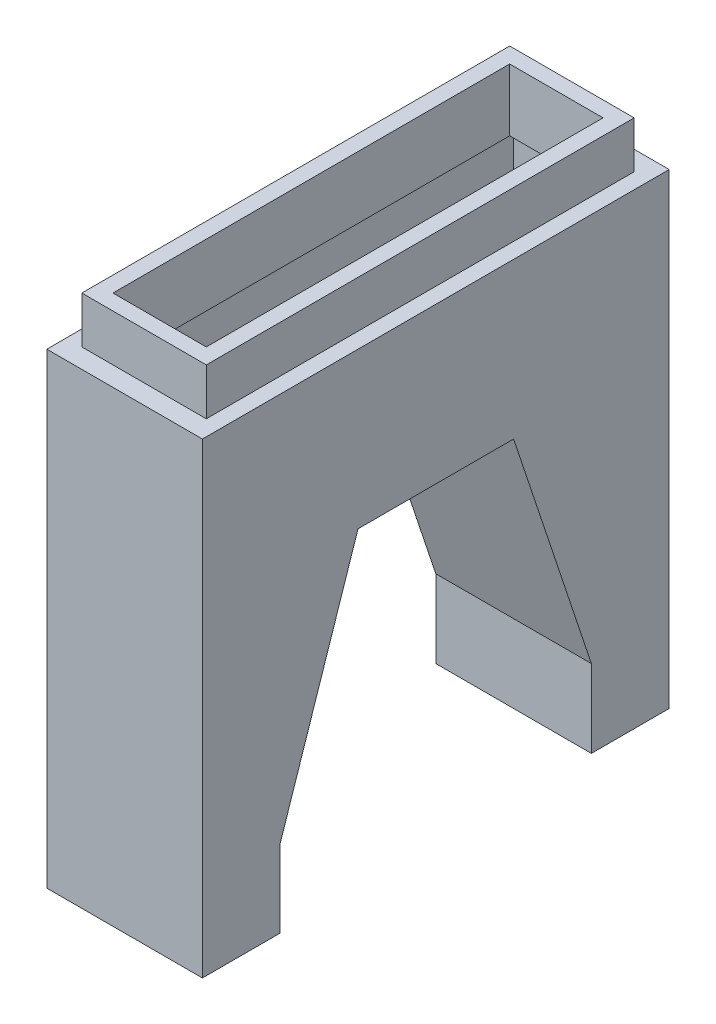
SolidWorks part; units mm, degrees
ref_plane "Front Plane" through (0, 0, 0) normal (0, 0, 1) x (1, 0, 0)
ref_plane "Top Plane" through (0, 0, 0) normal (0, 1, 0) x (1, 0, 0)
ref_plane "Right Plane" through (0, 0, 0) normal (1, 0, 0) x (0, 0, -1)
sketch "Sketch1" plane through (0, 0, 0) normal (0, 1, 0) x (1, 0, 0)
  line L1 (-4, -13.75) -> (4, -13.75)
  line L2 (-4, -13.75) -> (-4, 13.75)
  line L3 (-4, 13.75) -> (4, 13.75)
  line L4 (4, -13.75) -> (4, 13.75)
  line L5 (-4, -13.75) -> (4, 13.75) construction
  line L6 (-4, 13.75) -> (4, -13.75) construction
  point P0 (0, 0)
  dimension "D1" = 8
  dimension "D2" = 27.5
extrude "Boss-Extrude1" add sketch "Sketch1" along normal blind 3
sketch "Sketch2" plane through (0, 0, 0) normal (0, -1, 0) x (1, 0, 0)
  line L1 (-5, 15) -> (5, 15)
  line L2 (-5, 15) -> (-5, -15)
  line L3 (-5, -15) -> (5, -15)
  line L4 (5, 15) -> (5, -15)
  line L5 (-5, 15) -> (5, -15) construction
  line L6 (-5, -15) -> (5, 15) construction
  point P0 (0, 0)
  dimension "D1" = 10
  dimension "D2" = 30
extrude "Boss-Extrude2" add sketch "Sketch2" along normal blind 10
ref_plane "Plane1" through (0, 0, 0) normal (0, 0, 1) x (1, 0, 0)
sketch "Sketch4" plane through (0, -10, 0) normal (0, -1, 0) x (1, 0, 0)
  line L0 (-5, 15) -> (-5, -15) construction
  line L1 (5, 15) -> (-5, 15)
  line L2 (5, 15) -> (5, 10)
  line L3 (5, 10) -> (-5, 10)
  line L4 (-5, 15) -> (-5, 10)
  line L6 (5, -15) -> (-5, -15)
  line L7 (5, -15) -> (5, -10)
  line L8 (5, -10) -> (-5, -10)
  line L9 (-5, -15) -> (-5, -10)
  dimension "D1" = 5
  dimension "D2" = 5
extrude "Boss-Extrude3" add sketch "Sketch4" along normal blind 20
chamfer "Chamfer2" distance 5 distance2 15 2 edges at (0, -10, -10) (0, -10, 10) tangent propagation no first distance on face at (0, -10, 0)
sketch "Sketch7" plane through (0, 0, 10) normal (0, 0, -1) x (-1, 0, 0)
  line L0 (5, -25) -> (-5, -25) construction
  line L1 (5, -30) -> (1, -30)
  line L2 (5, -30) -> (5, -25)
  line L3 (5, -25) -> (1, -25)
  line L4 (1, -30) -> (1, -25)
  dimension "D1" = 4
extrude "Cut-Extrude2" cut sketch "Sketch7" against normal blind 2
shell "Shell1" thickness 1 removed face at (0, 3, 0) removed face at (-3, -27.5, 12) removed face at (-1, -27.5, 11) removed face at (-3, -25, 11)
